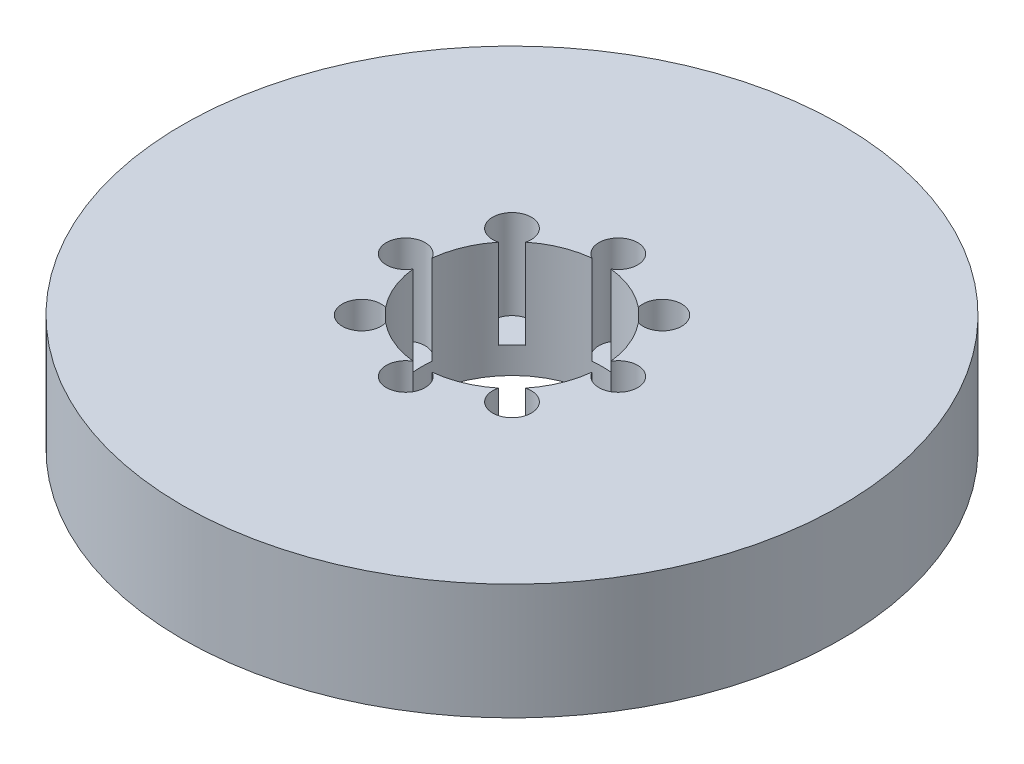
SolidWorks part; units mm, degrees
ref_plane "Front Plane" through (0, 0, 0) normal (0, 0, 1) x (1, 0, 0)
ref_plane "Top Plane" through (0, 0, 0) normal (0, 1, 0) x (1, 0, 0)
ref_plane "Right Plane" through (0, 0, 0) normal (1, 0, 0) x (0, 0, -1)
sketch "Sketch1" plane through (0, 0, 0) normal (0, 1, 0) x (1, 0, 0)
  circle A0 centre (0, 0) radius 82.5
  dimension "FLANGE_OD" = 165
extrude "Boss-Extrude1" add sketch "Sketch1" along normal blind 29
sketch "Sketch2" plane through (0, 0, 0) normal (0, 1, 0) x (1, 0, 0)
  circle A0 centre (0, 0) radius 22.5
  dimension "BORE_D" = 45
extrude "Cut-Extrude1" cut sketch "Sketch2" along normal through all
sketch "Sketch3" plane through (0, 29, 0) normal (0, 1, 0) x (1, 0, 0)
  circle A0 centre (0, 0) radius 26.6064 construction
  circle A1 centre (-26.6064, 0) radius 4.8501
  dimension "BOLT_D" = 9.7002
  dimension "BOLT_PCD" = 53.2128
extrude "Cut-Extrude2" cut sketch "Sketch3" against normal blind 22.356
pattern_circular "CirPattern1" count 8 over 360 about axis through (0, 0, 0) along (0, 1, 0) of "Cut-Extrude2"
